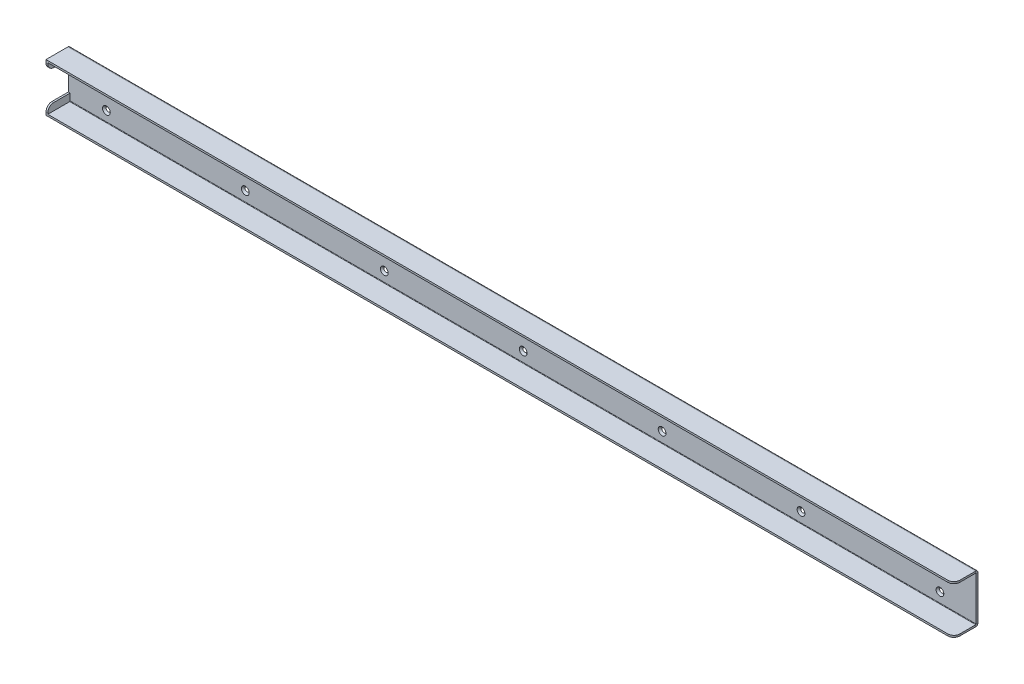
SolidWorks part; units mm, degrees
note: The reader was unsure of these and kept them because the rebuilt part matched: flange length of "边线-法兰1".
ref_plane "前视基准面" through (0, 0, 0) normal (0, 0, 1) x (1, 0, 0)
ref_plane "上视基准面" through (0, 0, 0) normal (0, 1, 0) x (1, 0, 0)
ref_plane "右视基准面" through (0, 0, 0) normal (1, 0, 0) x (0, 0, -1)
sketch "草图1" plane through (0, 0, 0) normal (0, 0, 1) x (1, 0, 0)
  line L1 (-750, 40) -> (750, 40)
  line L2 (-750, 40) -> (-750, -40)
  line L3 (-750, -40) -> (750, -40)
  line L4 (750, 40) -> (750, -40)
  line L5 (-750, 40) -> (750, -40) construction
  line L6 (-750, -40) -> (750, 40) construction
  point P0 (0, 0)
  dimension "D1" = 80
  dimension "D2" = 1500
base flange "基体-法兰1" sketch "草图1" thickness 3 reverse thickness direction no parameters "D1"=0.7366
edge flange "边线-法兰1" sketch "草图10" flange profiles "草图10", "草图11" flange angle 90 flange length 40 flange position material inside bend radius 0.7366 thickness 3 relief rectangular parameters "D6"=10, "D8"=1
sketch "草图10" plane through (0, -40, 0) normal (0, -1, 0) x (1, 0, 0)
  line L0 (-750, 0) -> (750, 0) construction
  line L1 (-750, 0) -> (750, 0)
  line L2 (-750, 0) -> (-750, 37)
  line L3 (-750, 37) -> (750, 37)
  line L4 (750, 37) -> (750, 0)
sketch "草图11" plane through (0, 40, 0) normal (0, 1, 0) x (-1, 0, 0)
  line L0 (-750, 0) -> (750, 0) construction
  line L1 (-750, 0) -> (750, 0)
  line L2 (-750, 0) -> (-750, 37)
  line L3 (-750, 37) -> (750, 37)
  line L4 (750, 37) -> (750, 0)
bend "边线折弯1" bend radius 0.7366 bend angle 90 parameters "D5"=1
bend "边线折弯2" bend radius 0.7366 bend angle 90 parameters "D5"=2
sketch "草图12" plane through (-750, 0, 0) normal (-1, 0, 0) x (0, 0, 1)
  line L0 (37, -40) -> (0.7366, -40) construction
  line L1 (0.7366, 40) -> (37, 40) construction
  line L2 (-3, 36.2634) -> (-3, -36.2634) construction
  line L3 (37, -40) -> (0.7366, -40)
  line L4 (0.7366, 40) -> (37, 40)
  line L5 (-3, 36.2634) -> (-3, -36.2634)
  line L6 (37, 40) -> (37, -40)
  arc A0 (-3, -36.2634) -> (0.7366, -40) centre (0.7366, -36.2634) ccw construction
  arc A1 (0.7366, 40) -> (-3, 36.2634) centre (0.7366, 36.2634) ccw construction
  arc A2 (-3, -36.2634) -> (0.7366, -40) centre (0.7366, -36.2634) ccw
  arc A3 (0.7366, 40) -> (-3, 36.2634) centre (0.7366, 36.2634) ccw
extrude "凸台-拉伸1" add sketch "草图12" along normal blind 3
sketch "草图13" plane through (-753, 0, 0) normal (-1, 0, 0) x (0, 0, 1)
  line L0 (37, -40) -> (37, 40) construction
  line L1 (74, 25) -> (0, 25)
  line L2 (74, 25) -> (74, -25)
  line L3 (74, -25) -> (0, -25)
  line L4 (0, 25) -> (0, -25)
  line L5 (74, 25) -> (0, -25) construction
  line L6 (74, -25) -> (0, 25) construction
  line L7 (-3, 36.2634) -> (-3, -36.2634) construction
  point P0 (37, 0)
  dimension "D1" = 3
  dimension "D2" = 50
extrude "切除-拉伸3" cut sketch "草图13" against normal blind 3
fillet "圆角1" radius 10 4 edges at (-751.5, 25, 37) (-751.5, -25, 37) (750, -38.5, 37) (750, 38.5, 37)
hole_wizard "打孔尺寸(%根据)内六角花形沉头螺钉的类型1" positions "草图14" profile "草图15" countersink size "M6" standard "GB"
sketch "草图14" plane through (0, 0, 0) normal (0, 0, 1) x (1, 0, 0)
  line L0 (0, -20) -> (0, 20) construction
  point P0 (0, 20)
  point P2 (0, -20)
  point P9 (0, 0)
  point P11 (0, -27.5339)
  point P12 (0, 27.5339)
  dimension "D1" = 40
sketch "草图15" plane through (0, 20, 0) normal (1, 0, 0) x (0, -1, 0)
  line L0 (0, 0) -> (0, 26.4828)
  line L1 (0, 26.4828) -> (3.3, 24.5)
  line L2 (3.3, 24.5) -> (3.3, 3.1)
  line L3 (3.3, 3.1) -> (6.4, 0)
  line L5 (6.4, 0) -> (0, 0)
  line L6 (-3.3, 3.1) -> (-6.4, 0) construction
  line L10 (0, 26.4828) -> (-3.3, 24.5) construction
  line L11 (0, -6.35) -> (0, 107.95) construction
  dimension "孔直径" = 6.6
  dimension "孔深度" = 24.5
  dimension "近端锥形沉头孔直径" = 12.8
  dimension "近端锥形沉头孔角度" = 90
  dimension "导头角度" = 118
pattern_linear "阵列(线性)1" count 4 spacing 230 along (-1, 0, 0) count 4 spacing 230 along (1, 0, 0) of "打孔尺寸(%根据)内六角花形沉头螺钉的类型1"
sketch "折弯-线1" plane through (0, 0, 0) normal (0, 1, 0) x (1, 0, 0)
sketch "边界框1" plane through (0, 0, 0) normal (0, 1, 0) x (1, 0, 0)
sheet metal parameters "钣金6" thickness 3 parameters "D1"=0.7366
flat pattern "平板型式6" [suppressed]
sketch "折弯-线2" plane through (0, 0, 0) normal (0, 1, 0) x (1, 0, 0)
sketch "边界框2" [suppressed] plane through (0, 0, 0) normal (0, 1, 0) x (1, 0, 0)
sheet metal parameters "钣金7" thickness 3 parameters "D1"=0.7366
flat pattern "平板型式6" [suppressed]
sketch "折弯-线2" plane through (0, 0, 0) normal (0, 1, 0) x (1, 0, 0)
sketch "边界框2" [suppressed] plane through (0, 0, 0) normal (0, 1, 0) x (1, 0, 0)
bend of the flat pattern "展平-<边线折弯1>1"
bend of the flat pattern "展平-<边线折弯2>1"
sheet metal parameters "钣金8" thickness 3 parameters "D1"=0.7366
flat pattern "平板型式6" [suppressed]
sketch "折弯-线2" plane through (0, 0, 0) normal (0, 1, 0) x (1, 0, 0)
sketch "边界框2" [suppressed] plane through (0, 0, 0) normal (0, 1, 0) x (1, 0, 0)
bend of the flat pattern "展平-<边线折弯1>1"
bend of the flat pattern "展平-<边线折弯2>1"
sheet metal parameters "钣金9" thickness 3 parameters "D1"=0.7366
flat pattern "平板型式6" [suppressed]
sketch "折弯-线2" plane through (0, 0, 0) normal (0, 1, 0) x (1, 0, 0)
sketch "边界框2" [suppressed] plane through (0, 0, 0) normal (0, 1, 0) x (1, 0, 0)
bend of the flat pattern "展平-<边线折弯1>1"
bend of the flat pattern "展平-<边线折弯2>1"
sheet metal parameters "钣金10" thickness 3 parameters "D1"=0.7366
flat pattern "平板型式6" [suppressed]
sketch "折弯-线2" plane through (0, 0, 0) normal (0, 1, 0) x (1, 0, 0)
sketch "边界框2" [suppressed] plane through (0, 0, 0) normal (0, 1, 0) x (1, 0, 0)
bend of the flat pattern "展平-<边线折弯1>1"
bend of the flat pattern "展平-<边线折弯2>1"
sheet metal parameters "钣金11" thickness 3 parameters "D1"=0.7366
flat pattern "平板型式6" [suppressed]
sketch "折弯-线2" plane through (0, 0, 0) normal (0, 1, 0) x (1, 0, 0)
sketch "边界框2" [suppressed] plane through (0, 0, 0) normal (0, 1, 0) x (1, 0, 0)
bend of the flat pattern "展平-<边线折弯1>1"
bend of the flat pattern "展平-<边线折弯2>1"
